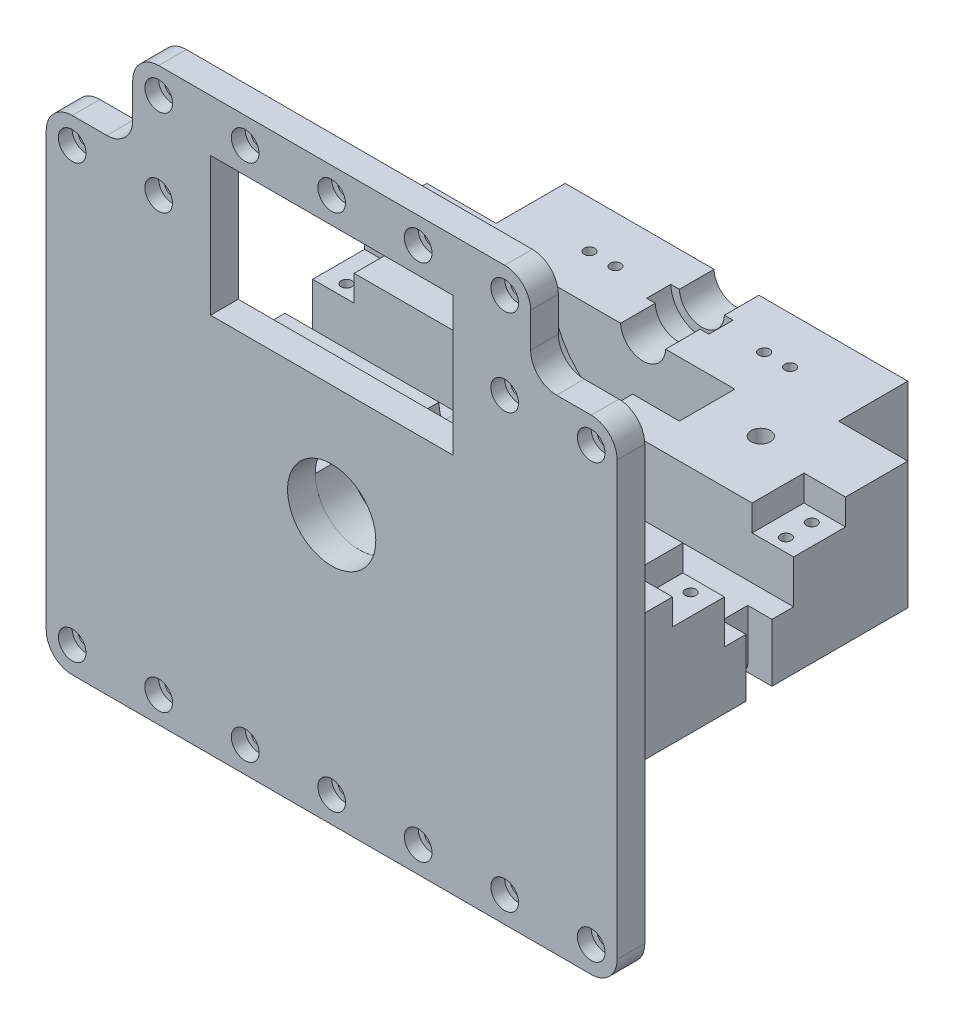
SolidWorks part; units mm, degrees
ref_plane "Front Plane" through (0, 0, 0) normal (0, 0, 1) x (1, 0, 0)
ref_plane "Top Plane" through (0, 0, 0) normal (0, 1, 0) x (1, 0, 0)
ref_plane "Right Plane" through (0, 0, 0) normal (1, 0, 0) x (0, 0, -1)
sketch "Sketch2" plane through (0, 0, 0) normal (0, 0, 1) x (1, 0, 0)
  line L5 (-57.5, 60) -> (-57.5, 50)
  line L6 (-75, -97.5) -> (75, -97.5)
  line L24 (-82.5, -90) -> (-82.5, 35)
  line L25 (-50, 67.5) -> (50, 67.5)
  line L26 (82.5, -90) -> (82.5, 35)
  line L27 (0, -100) -> (0, 100) construction
  line L28 (-100, 0) -> (100, 0) construction
  line L29 (-65, 42.5) -> (-75, 42.5)
  line L34 (57.5, 60) -> (57.5, 50)
  line L35 (65, 42.5) -> (75, 42.5)
  arc A12 (-82.5, 35) -> (-75, 42.5) centre (-75, 35) cw
  arc A19 (82.5, 35) -> (75, 42.5) centre (75, 35) ccw
  arc A20 (65, 42.5) -> (57.5, 50) centre (65, 50) cw
  arc A21 (57.5, 60) -> (50, 67.5) centre (50, 60) ccw
  arc A22 (-50, 67.5) -> (-57.5, 60) centre (-50, 60) ccw
  arc A23 (-65, 42.5) -> (-57.5, 50) centre (-65, 50) ccw
  arc A24 (-82.5, -90) -> (-75, -97.5) centre (-75, -90) ccw
  arc A25 (82.5, -90) -> (75, -97.5) centre (75, -90) cw
  point P0 (0, 0)
  point P39 (-57.5, 67.5)
  dimension "D5" = 25
  dimension "D6" = 82.5
  dimension "D7" = 7.5
  dimension "D2" = 25
  dimension "D3" = 165
  dimension "D8" = 7.5
  dimension "D1" = 67.5
  dimension "D4" = 82.5
extrude "Boss-Extrude1" add sketch "Sketch2" against normal blind 8
sketch "Sketch3" plane through (0, 0, 0) normal (0, 0, 1) x (1, 0, 0)
  line L0 (0, 100) -> (0, -100) construction
  circle A0 centre (0, -20) radius 12.75
  dimension "D1" = 25.5
  dimension "D2" = 20
extrude "Cut-Extrude1" cut sketch "Sketch3" against normal up to surface (8 mm away) up to face at (0, 13.75, -8)
sketch "Sketch5" plane through (0, 0, -8) normal (0, 0, -1) x (-1, 0, 0)
  line L3 (-69.5, -87) -> (-69.5, -20)
  line L4 (0, 67.5) -> (0, -97.5) construction
  line L5 (-82.5, -90) -> (-82.5, 35) construction
  line L6 (-69.5, -20) -> (69.5, -20)
  line L7 (-69.5, -87) -> (69.5, -87)
  line L8 (75, -97.5) -> (-75, -97.5) construction
  line L9 (69.5, -87) -> (69.5, -20)
  line L10 (-50, 67.5) -> (50, 67.5) construction
  point P10 (0, -87)
  point P11 (0, -20)
  dimension "D1" = 10.5
  dimension "D2" = 67
  dimension "D3" = 13
extrude "Boss-Extrude2" add sketch "Sketch5" along normal blind 109
sketch "Sketch6" plane through (0, 0, -8) normal (0, 0, -1) x (-1, 0, 0)
  circle A0 centre (0, -20) radius 26.5
  circle A1 centre (0, -20) radius 12.75 construction
  dimension "D1" = 53
extrude "Cut-Extrude2" cut sketch "Sketch6" along normal blind 16 from offset 10
sketch "Sketch7" plane through (0, 0, -8) normal (0, 0, -1) x (-1, 0, 0)
  circle A0 centre (0, -20) radius 6.5
  circle A1 centre (0, -20) radius 12.75 construction
  dimension "D1" = 13
extrude "Cut-Extrude3" cut sketch "Sketch7" along normal up to surface (109 mm away) up to face at (0, -53.5, -117)
sketch "Sketch10" plane through (0, 0, -8) normal (0, 0, -1) x (-1, 0, 0)
  line L0 (-69.5, -20) -> (-69.5, -20.25)
  line L1 (-69.5, -20) -> (-69.5, -87) construction
  line L2 (-69.5, -20.25) -> (69.5, -20.25)
  line L3 (69.5, -87) -> (69.5, -20) construction
  line L4 (69.5, -20.25) -> (69.5, -20)
  line L5 (69.5, -20) -> (-69.5, -20)
  dimension "D1" = 0.25
extrude "Cut-Extrude4" cut sketch "Sketch10" along normal up to surface (109 mm away) up to face at (0, -43.4167, -117)
sketch "Sketch11" plane through (0, 0, -8) normal (0, 0, -1) x (-1, 0, 0)
  line L0 (-69.5, -72) -> (-54.5, -72)
  line L1 (-69.5, -20.25) -> (-69.5, -87) construction
  line L2 (-54.5, -72) -> (-54.5, -87)
  line L3 (-69.5, -87) -> (69.5, -87) construction
  line L4 (-69.5, -72) -> (-69.5, -87)
  line L5 (-69.5, -87) -> (-54.5, -87)
  line L11 (0, 87.7767) -> (0, -101.3295) construction
  line L12 (69.5, -87) -> (54.5, -87)
  line L13 (69.5, -72) -> (69.5, -87)
  line L14 (54.5, -72) -> (54.5, -87)
  line L15 (69.5, -72) -> (54.5, -72)
  dimension "D1" = 15
  dimension "D2" = 15
sketch "Sketch14" plane through (69.5, 0, 0) normal (1, 0, 0) x (0, 0, -1)
  line L0 (44, 4.6823) -> (44, -72.994) construction
  line L2 (64, 4.6823) -> (64, -72.994) construction
  line L3 (8, -90) -> (8, 35) construction
  line L4 (74, 4.6823) -> (74, -72.994) construction
  line L5 (90, 4.6823) -> (90, -72.994) construction
  line L6 (100, 4.6823) -> (100, -72.994) construction
  dimension "D1" = 36
  dimension "D2" = 20
  dimension "D3" = 10
  dimension "D4" = 16
  dimension "D5" = 10
sketch "Sketch15" plane through (0, 0, -8) normal (0, 0, -1) x (-1, 0, 0)
  circle A0 centre (0, -20) radius 32.5
  circle A1 centre (0, -20) radius 12.75 construction
  dimension "D1" = 65
extrude "Cut-Extrude8" cut sketch "Sketch15" along normal blind 20 from offset 36
sketch "Sketch16" plane through (69.5, 0, 0) normal (1, 0, 0) x (0, 0, -1)
  line L0 (44, -20.25) -> (44, -40.25)
  line L1 (44, 4.6823) -> (44, -72.994) construction
  line L2 (44, -40.25) -> (64, -40.25)
  line L3 (64, 4.6823) -> (64, -72.994) construction
  line L4 (64, -40.25) -> (64, -20.25)
  line L5 (64, -20.25) -> (44, -20.25)
  dimension "D1" = 20
extrude "Cut-Extrude9" cut sketch "Sketch16" against normal through all both and the other way through all
sketch "Sketch17" plane through (0, 0, -8) normal (0, 0, -1) x (-1, 0, 0)
  circle A0 centre (0, -20) radius 26.5
  circle A1 centre (0, -20) radius 12.75 construction
  dimension "D1" = 53
extrude "Cut-Extrude10" cut sketch "Sketch17" along normal blind 26 from surface starting at face at (0, -32.5625, -64)
sketch "Sketch20" plane through (0, 0, -8) normal (0, 0, -1) x (-1, 0, 0)
  line L0 (-69.5, -20.25) -> (-69.5, -87)
  line L1 (-69.5, -87) -> (69.5, -87)
  line L2 (69.5, -87) -> (69.5, -20.25)
  line L3 (69.5, -20.25) -> (-69.5, -20.25)
  line L4 (-69.5, -20.25) -> (-6.4952, -20.25) construction
  line L5 (-69.5, 4.6823) -> (-69.5, -72.994) construction
  line L6 (69.5, -87) -> (69.5, -20.25) construction
  line L7 (-69.5, -87) -> (69.5, -87) construction
extrude "Boss-Extrude6" add sketch "Sketch20" along normal blind 10 from surface starting at face at (0, -35.0625, -64)
sketch "Sketch21" plane through (0, 0, -8) normal (0, 0, -1) x (-1, 0, 0)
  circle A0 centre (0, -20) radius 13
  circle A1 centre (0, -20) radius 12.75 construction
  dimension "D1" = 26
extrude "Cut-Extrude12" cut sketch "Sketch21" along normal up to surface (66 mm away) up to face at (0, -33.375, -74)
fillet "Fillet1" radius 5 1 edges at (25.4202, -40.25, -54) type face fillet first side face at (47.4601, -40.25, -54) second side face at (0, -46.375, -54)
fillet "Fillet2" radius 5 1 edges at (-25.4202, -40.25, -54) type face fillet first side face at (-47.4601, -40.25, -54) second side face at (-0.8844, -46.7745, -54)
sketch "Sketch22" plane through (0, 0, -8) normal (0, 0, -1) x (-1, 0, 0)
  circle A0 centre (0, -20) radius 9
  circle A1 centre (0, -20) radius 12.75 construction
  dimension "D1" = 18
extrude "Cut-Extrude13" cut sketch "Sketch22" against normal blind 17 and the other way through all from surface starting at face at (0, -43.5417, -117)
sketch "Sketch23" plane through (0, 0, -117) normal (0, 0, -1) x (-1, 0, 0)
  line L0 (-8.9965, -20.25) -> (-6.4952, -20.25)
  line L1 (6.4952, -20.25) -> (8.9965, -20.25)
  arc A0 (-8.9965, -20.25) -> (8.9965, -20.25) centre (0, -20) ccw
  arc A1 (-6.4952, -20.25) -> (6.4952, -20.25) centre (0, -20) ccw
  arc A2 (-6.4952, -20.25) -> (6.4952, -20.25) centre (0, -20) ccw construction
  arc A3 (-8.9965, -20.25) -> (8.9965, -20.25) centre (0, -20) ccw construction
extrude "Boss-Extrude7" add sketch "Sketch23" against normal blind 10
sketch "Sketch24" plane through (0, 0, -117) normal (0, 0, -1) x (-1, 0, 0)
  line L0 (-69.5, -57) -> (-69.5, -87)
  line L1 (-69.5, 4.6823) -> (-69.5, -72.994) construction
  line L2 (-69.5, -87) -> (-39.5, -87)
  line L3 (-69.5, -87) -> (69.5, -87) construction
  line L4 (-39.5, -87) -> (-39.5, -57)
  line L5 (-39.5, -57) -> (-69.5, -57)
  line L6 (0, 119.6824) -> (0, -123.2201) construction
  line L7 (39.5, -57) -> (69.5, -57)
  line L8 (39.5, -87) -> (39.5, -57)
  line L9 (69.5, -87) -> (39.5, -87)
  line L10 (69.5, -57) -> (69.5, -87)
  dimension "D1" = 30
  dimension "D2" = 30
extrude "Cut-Extrude14" cut sketch "Sketch24" against normal up to surface (109 mm away) up to face at (0, -44.625, -8)
sketch "Sketch25" plane through (39.5, 0, 0) normal (1, 0, 0) x (0, 0, -1)
  line L0 (8, -57) -> (8, -87)
  line L1 (8, -87) -> (38, -87)
  line L2 (8, -87) -> (117, -87) construction
  line L3 (38, -87) -> (38, -57)
  line L4 (8, -57) -> (117, -57) construction
  line L5 (38, -57) -> (8, -57)
  line L6 (74, -57) -> (74, -87)
  line L7 (74, 4.6823) -> (74, -72.994) construction
  line L8 (74, -87) -> (117, -87)
  line L9 (117, -87) -> (117, -57)
  line L10 (117, -57) -> (74, -57)
  dimension "D1" = 30
extrude "Cut-Extrude15" cut sketch "Sketch25" against normal through all both and the other way through all
sketch "Sketch27" plane through (0, -20.25, 0) normal (0, 1, 0) x (1, 0, 0)
  point P0 (-42.0234, 82)
  point P1 (42.0234, 82)
  point P3 (-42.0234, 26)
  point P5 (42.0234, 26)
  point P7 (-28.9894, 103.5)
  point P9 (-21.4894, 103.5)
  point P11 (21.4894, 103.5)
  point P13 (28.9894, 103.5)
sketch "Sketch29" plane through (69.5, 0, 0) normal (1, 0, 0) x (0, 0, -1)
  line L0 (44, -20.25) -> (44, -27.75)
  line L1 (44, -40.25) -> (44, -20.25) construction
  line L2 (44, -27.75) -> (29, -27.75)
  line L3 (29, -27.75) -> (29, -20.25)
  line L4 (44, -20.25) -> (8, -20.25) construction
  line L5 (29, -20.25) -> (44, -20.25)
  line L6 (64, -20.25) -> (64, -27.75)
  line L7 (64, -20.25) -> (64, -40.25) construction
  line L8 (64, -27.75) -> (79, -27.75)
  line L9 (79, -27.75) -> (79, -20.25)
  line L10 (117, -20.25) -> (64, -20.25) construction
  line L11 (79, -20.25) -> (64, -20.25)
  dimension "D1" = 15
  dimension "D2" = 7.5
  dimension "D3" = 15
  dimension "D4" = 7.5
extrude "Cut-Extrude16" cut sketch "Sketch29" against normal blind 12 and the other way through all
sketch "Sketch30" plane through (-69.5, 0, 0) normal (-1, 0, 0) x (0, 0, 1)
  line L0 (-44, -20.25) -> (-29, -20.25)
  line L1 (-44, -20.25) -> (-8, -20.25) construction
  line L2 (-29, -20.25) -> (-29, -27.75)
  line L3 (-29, -27.75) -> (-44, -27.75)
  line L4 (-44, -20.25) -> (-44, -40.25) construction
  line L5 (-44, -27.75) -> (-44, -20.25)
  line L6 (-64, -27.75) -> (-79, -27.75)
  line L7 (-64, -40.25) -> (-64, -20.25) construction
  line L8 (-79, -27.75) -> (-79, -20.25)
  line L9 (-117, -20.25) -> (-64, -20.25) construction
  line L10 (-79, -20.25) -> (-64, -20.25)
  line L11 (-64, -20.25) -> (-64, -27.75)
  dimension "D1" = 15
  dimension "D2" = 15
  dimension "D3" = 7.5
extrude "Cut-Extrude17" cut sketch "Sketch30" against normal blind 12
sketch "Sketch31" plane through (-69.5, 0, 0) normal (-1, 0, 0) x (0, 0, 1)
  line L7 (-57.75, -40.25) -> (-50.25, -40.25)
  line L9 (-44, -40.25) -> (-64, -40.25) construction
  line L11 (-50.25, -40.25) -> (-50.25, -57)
  line L12 (-8, -57) -> (-117, -57) construction
  line L13 (-50.25, -57) -> (-57.75, -57)
  line L14 (-57.75, -57) -> (-57.75, -40.25)
  line L15 (-57.75, -30.25) -> (-57.75, -40.25) construction
  line L16 (-50.25, -40.25) -> (-50.25, -30.25) construction
extrude "Cut-Extrude18" cut sketch "Sketch31" against normal blind 7
sketch "Sketch32" plane through (69.5, 0, 0) normal (1, 0, 0) x (0, 0, -1)
  line L0 (50.25, -40.25) -> (57.75, -40.25)
  line L1 (57.75, -40.25) -> (57.75, -57)
  line L2 (8, -57) -> (117, -57) construction
  line L3 (57.75, -57) -> (50.25, -57)
  line L4 (50.25, -57) -> (50.25, -40.25)
  line L5 (64, -40.25) -> (44, -40.25) construction
  line L6 (50.25, -30.25) -> (50.25, -40.25) construction
  line L7 (57.75, -40.25) -> (57.75, -30.25) construction
  dimension "D1" = 7.5
extrude "Cut-Extrude19" cut sketch "Sketch32" against normal blind 7
sketch "Sketch34" plane through (0, -20.25, 0) normal (0, 1, 0) x (1, 0, 0)
  point P0 (-63.5, 75.25)
  point P1 (-63.5, 67.75)
  point P3 (-63.5, 40.25)
  point P5 (-63.5, 32.75)
  point P7 (63.5, 75.25)
  point P9 (63.5, 67.75)
  point P11 (63.5, 40.25)
  point P13 (63.5, 32.75)
  point P15 (28.9894, 103.5)
  point P17 (21.4894, 103.5)
  point P19 (-28.9894, 103.5)
  point P21 (-21.4894, 103.5)
hole_wizard "Ø1.0mm Dowel Hole2" positions "Sketch34" profile "Sketch35" hole size "Ø1.0" standard "ANSI Metric"
sketch "Sketch35" plane through (-63.5, -20.25, -75.25) normal (1, 0, 0) x (0, 0, 1)
  line L0 (0, 0) -> (0, 25.9313)
  line L1 (0, 25.9313) -> (1.55, 25)
  line L2 (1.55, 25) -> (1.55, 0)
  line L5 (1.55, 0) -> (0, 0)
  line L10 (0, 25.9313) -> (-1.55, 25) construction
  line L11 (0, -6.35) -> (0, 107.95) construction
  dimension "Hole Dia." = 3.1
  dimension "Hole Depth" = 25
  dimension "Drill Angle" = 118
sketch "Sketch36" plane through (0, -20.25, 0) normal (0, 1, 0) x (1, 0, 0)
  point P0 (-42.0234, 82)
  point P3 (-42.0234, 26)
  point P6 (42.0234, 26)
  point P9 (42.0234, 82)
hole_wizard "Ø1.0mm Dowel Hole3" positions "Sketch36" profile "Sketch37" hole size "Ø1.0" standard "ANSI Metric"
sketch "Sketch37" plane through (-42.0234, -20.25, -82) normal (1, 0, 0) x (0, 0, 1)
  line L0 (0, 0) -> (0, 26.6824)
  line L1 (0, 26.6824) -> (2.8, 25)
  line L2 (2.8, 25) -> (2.8, 0)
  line L5 (2.8, 0) -> (0, 0)
  line L10 (0, 26.6824) -> (-2.8, 25) construction
  line L11 (0, -6.35) -> (0, 107.95) construction
  dimension "Hole Dia." = 5.6
  dimension "Hole Depth" = 25
  dimension "Drill Angle" = 118
sketch "Sketch38" plane through (0, -20.25, 0) normal (0, 1, 0) x (1, 0, 0)
  line L0 (49.5, 117) -> (49.5, 97)
  line L1 (69.5, 117) -> (6.4952, 117) construction
  line L2 (49.5, 97) -> (69.5, 97)
  line L3 (69.5, 117) -> (69.5, 79) construction
  line L4 (69.5, 97) -> (69.5, 117)
  line L5 (69.5, 117) -> (49.5, 117)
  line L6 (-69.5, 117) -> (-49.5, 117)
  line L7 (-6.4952, 117) -> (-69.5, 117) construction
  line L8 (-49.5, 117) -> (-49.5, 97)
  line L10 (-49.5, 97) -> (-69.5, 97)
  line L11 (-69.5, 117) -> (-69.5, 79) construction
  line L12 (-69.5, 97) -> (-69.5, 117)
  dimension "D1" = 20
  dimension "D2" = 20
  dimension "D3" = 20
  dimension "D4" = 20
extrude "Cut-Extrude20" cut sketch "Sketch38" against normal through all
fillet "Fillet3" radius 2 1 edges at (62.5, -57, -54) type face fillet first side face at (62.5, -48.625, -54) second side face at (0, -57, -56)
fillet "Fillet4" radius 2 1 edges at (-62.5, -57, -54) type face fillet first side face at (-62.5, -48.625, -54) second side face at (0, -57, -56)
sketch "Sketch39" plane through (0, 0, -74) normal (0, 0, -1) x (-1, 0, 0)
  line L0 (-39.5, -81.5) -> (-39.5, -87)
  line L1 (-39.5, -87) -> (-39.5, -57) construction
  line L2 (-39.5, -87) -> (39.5, -87)
  line L3 (39.5, -87) -> (39.5, -81.5)
  line L4 (39.5, -57) -> (39.5, -87) construction
  line L5 (39.5, -81.5) -> (-39.5, -81.5)
  line L6 (72.5, -82.5) -> (-72.5, -82.5) construction
  dimension "D1" = 1
extrude "Cut-Extrude21" cut sketch "Sketch39" against normal up to surface (36 mm away) up to face at (0, -72, -38)
sketch "Sketch41" plane through (0, 0, 0) normal (0, 0, 1) x (1, 0, 0)
  point P0 (-75, 35)
  point P3 (-50, 35)
  point P6 (-50, 60)
  point P9 (-25, 60)
  point P12 (0, 60)
  point P15 (25, 60)
  point P18 (50, 60)
  point P21 (50, 35)
  point P24 (75, 35)
  point P28 (-75, -90)
  point P31 (-50, -90)
  point P34 (-25, -90)
  point P37 (0, -90)
  point P40 (25, -90)
  point P43 (50, -90)
  point P46 (75, -90)
hole_wizard "CBORE for M4 SHCS1" positions "Sketch41" profile "Sketch42" counterbore size "M4" standard "ANSI Metric" end condition through all
sketch "Sketch42" plane through (-75, 35, 0) normal (1, 0, 0) x (0, -1, 0)
  line L0 (0, 0) -> (0, 117)
  line L1 (0, 117) -> (2.25, 117)
  line L3 (2.25, 117) -> (2.25, 4)
  line L4 (2.25, 4) -> (4, 4)
  line L5 (4, 4) -> (4, 0)
  line L7 (4, 0) -> (0, 0)
  line L11 (0, -6.35) -> (0, 107.95) construction
  dimension "Thru Hole Dia." = 4.5
  dimension "Thru Hole Depth" = 117
  dimension "C'Bore Dia." = 8
  dimension "C'Bore Depth" = 4
sketch "Sketch43" plane through (0, 0, 0) normal (0, 0, 1) x (1, 0, 0)
  line L0 (-35, 52.5) -> (35, 52.5)
  line L1 (35, 52.5) -> (35, 12.5)
  line L2 (35, 12.5) -> (-35, 12.5)
  line L3 (-35, 12.5) -> (-35, 52.5)
  line L4 (50, 67.5) -> (-50, 67.5) construction
  line L6 (82.5, -90) -> (82.5, 35) construction
  dimension "D1" = 15
  dimension "D2" = 70
  dimension "D3" = 47.5
  dimension "D4" = 40
extrude "Cut-Extrude22" cut sketch "Sketch43" against normal through all both and the other way through all
